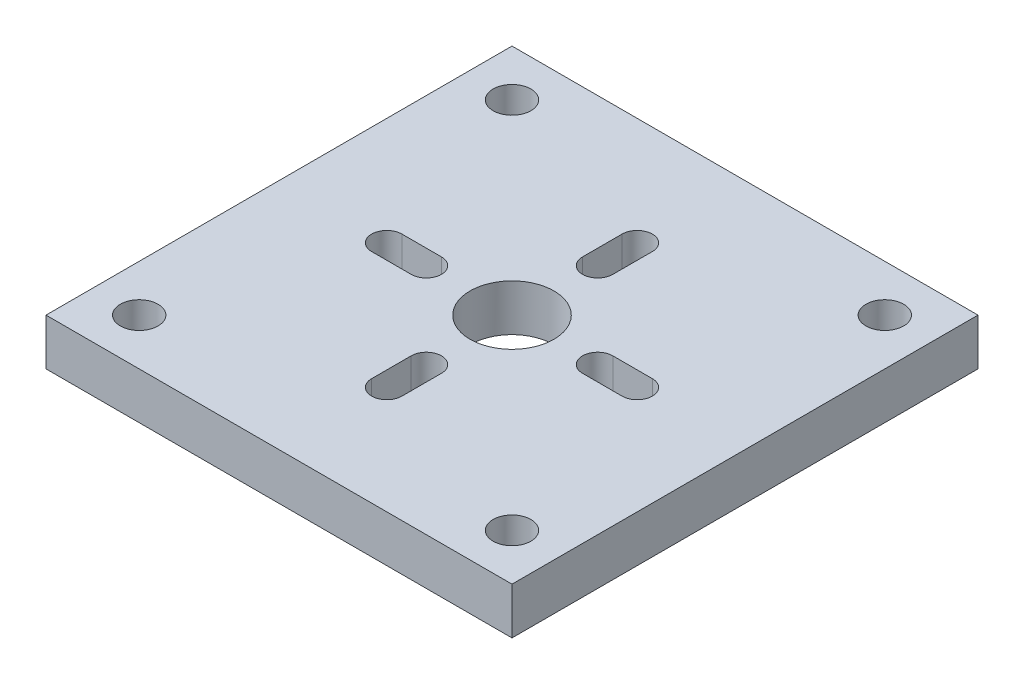
SolidWorks part; units mm, degrees
ref_plane "Front Plane" through (0, 0, 0) normal (0, 0, 1) x (1, 0, 0)
ref_plane "Top Plane" through (0, 0, 0) normal (0, 1, 0) x (1, 0, 0)
ref_plane "Right Plane" through (0, 0, 0) normal (1, 0, 0) x (0, 0, -1)
sketch "Sketch1" plane through (0, 0, 0) normal (0, 1, 0) x (1, 0, 0)
  line L1 (50, 50) -> (-50, 50)
  line L2 (50, 50) -> (50, -50)
  line L3 (50, -50) -> (-50, -50)
  line L4 (-50, 50) -> (-50, -50)
  line L5 (50, 50) -> (-50, -50) construction
  line L6 (50, -50) -> (-50, 50) construction
  point P0 (0, 0)
  dimension "D1" = 100
  dimension "D2" = 100
extrude "base" add sketch "Sketch1" along normal blind 10 contours L1 L4 L3 L2
sketch "Sketch2" plane through (0, 10, 0) normal (0, 1, 0) x (1, 0, 0)
  circle A0 centre (0, 0) radius 9
  dimension "D1" = 18
extrude "actuator cut" cut sketch "Sketch2" against normal blind 40
sketch "Sketch3" plane through (0, 10, 0) normal (0, 1, 0) x (1, 0, 0)
  line L0 (0, -26.8701) -> (0, -18.3848) construction
  line L1 (0, 0) -> (0, 19) construction
  line L2 (3.25, -26.8701) -> (3.25, -18.3848)
  line L8 (0, 0) -> (19, 0) construction
  line L12 (-3.25, -26.8701) -> (-3.25, -18.3848)
  line L17 (26.8701, 0) -> (18.3848, 0) construction
  line L18 (26.8701, 3.25) -> (18.3848, 3.25)
  line L19 (26.8701, -3.25) -> (18.3848, -3.25)
  line L20 (-26.8701, 0) -> (-18.3848, 0) construction
  line L21 (-26.8701, -3.25) -> (-18.3848, -3.25)
  line L22 (-26.8701, 3.25) -> (-18.3848, 3.25)
  line L23 (0, 26.8701) -> (0, 18.3848) construction
  line L24 (-3.25, 26.8701) -> (-3.25, 18.3848)
  line L25 (3.25, 26.8701) -> (3.25, 18.3848)
  arc A16 (26.8701, 3.25) -> (26.8701, -3.25) centre (26.8701, 0) cw
  arc A17 (18.3848, -3.25) -> (18.3848, 3.25) centre (18.3848, 0) cw
  arc A18 (3.25, -26.8701) -> (-3.25, -26.8701) centre (0, -26.8701) cw
  arc A19 (-3.25, -18.3848) -> (3.25, -18.3848) centre (0, -18.3848) cw
  arc A20 (-26.8701, -3.25) -> (-26.8701, 3.25) centre (-26.8701, 0) cw
  arc A21 (-18.3848, 3.25) -> (-18.3848, -3.25) centre (-18.3848, 0) cw
  arc A22 (-3.25, 26.8701) -> (3.25, 26.8701) centre (0, 26.8701) cw
  arc A23 (3.25, 18.3848) -> (-3.25, 18.3848) centre (0, 18.3848) cw
  point P5 (0, -22.6274)
  point P15 (-22.6274, 0)
  point P23 (0, 22.6274)
  point P30 (22.6274, 0)
  point P35 (0, 0)
  dimension "D1" = 26.8701
  dimension "D3" = 3.25
  dimension "D2" = 18.3848
  dimension "D4" = 4
  dimension "D7" = 0
extrude "Cut-Extrude1" cut sketch "Sketch3" against normal up to next
sketch "Sketch4" [suppressed] plane through (0, 0, 0) normal (0, -1, 0) x (1, 0, 0)
  line L0 (2.373, 19) -> (2.373, 13) construction
  line L1 (-4.127, 13) -> (-4.127, 19) construction
  line L2 (13, 6.377) -> (19, 6.377)
  line L3 (19, -5.123) -> (13, -5.123)
  line L4 (6.377, -13.25) -> (6.377, -19.25)
  line L5 (-5.123, -19.25) -> (-5.123, -13.25)
  line L6 (-13.25, -6.627) -> (-19.25, -6.627)
  line L7 (-19.25, 4.873) -> (-13.25, 4.873)
  line L8 (2.373, 19) -> (2.373, 13) construction
  line L9 (-4.127, 13) -> (-4.127, 19) construction
  line L16 (4.873, 19) -> (4.873, 13)
  line L17 (-6.627, 13) -> (-6.627, 19)
  arc A0 (-4.127, 13) -> (2.373, 13) centre (-0.877, 13) ccw construction
  arc A1 (2.373, 19) -> (-4.127, 19) centre (-0.877, 19) ccw construction
  arc A2 (13, 6.377) -> (13, -5.123) centre (13, 0.627) ccw
  arc A3 (19, -5.123) -> (19, 6.377) centre (19, 0.627) ccw
  arc A4 (6.377, -13.25) -> (-5.123, -13.25) centre (0.627, -13.25) ccw
  arc A5 (-5.123, -19.25) -> (6.377, -19.25) centre (0.627, -19.25) ccw
  arc A6 (-13.25, -6.627) -> (-13.25, 4.873) centre (-13.25, -0.877) ccw
  arc A7 (-19.25, 4.873) -> (-19.25, -6.627) centre (-19.25, -0.877) ccw
  arc A8 (-4.127, 13) -> (2.373, 13) centre (-0.877, 13) ccw construction
  arc A9 (2.373, 19) -> (-4.127, 19) centre (-0.877, 19) ccw construction
  arc A16 (-6.627, 13) -> (4.873, 13) centre (-0.877, 13) ccw
  arc A17 (4.873, 19) -> (-6.627, 19) centre (-0.877, 19) ccw
  point P33 (-0.125, -0.125)
  dimension "D1" = 2.5
  dimension "D2" = 4
split line "Split Line1" [suppressed]
sketch "Sketch5" plane through (0, 10, 0) normal (0, 1, 0) x (1, 0, 0)
  line L0 (-40, 40) -> (-40, -40) construction
  line L1 (-40, -40) -> (40, -40) construction
  circle A0 centre (-40, -40) radius 4.05
  circle A1 centre (-40, 40) radius 4.05
  circle A2 centre (40, -40) radius 4.05
  circle A3 centre (40, 40) radius 4.05
  point P8 (-40, 0)
  point P9 (0, -40)
  dimension "D3" = 8.1
  dimension "D1" = 80
  dimension "D2" = 80
extrude "Cut-Extrude2" cut sketch "Sketch5" against normal up to next
sketch "Sketch6" [suppressed] plane through (0, 0, 0) normal (0, -1, 0) x (1, 0, 0)
  circle A0 centre (-40, 40) radius 4
  circle A1 centre (40, 40) radius 4
  circle A2 centre (40, -40) radius 4
  circle A3 centre (-40, -40) radius 4
  dimension "D1" = 8
extrude "Cut-Extrude3" [suppressed] cut sketch "Sketch6" against normal through all
sketch "Sketch7" [suppressed] plane through (0, 0, 0) normal (0, -1, 0) x (1, 0, 0)
  line L175 (6.25, -26.8701) -> (6.25, -18.3848)
  line L176 (-6.25, -18.3848) -> (-6.25, -26.8701)
  line L177 (18.3848, -6.25) -> (26.8701, -6.25)
  line L178 (26.8701, 6.25) -> (18.3848, 6.25)
  line L179 (18.3848, -6.25) -> (26.8701, -6.25)
  line L180 (26.8701, 6.25) -> (18.3848, 6.25)
  line L181 (-26.8701, -6.25) -> (-18.3848, -6.25)
  line L182 (-18.3848, 6.25) -> (-26.8701, 6.25)
  line L183 (-6.25, 26.8701) -> (-6.25, 18.3848)
  line L184 (6.25, 18.3848) -> (6.25, 26.8701)
  arc A173 (-6.25, -26.8701) -> (6.25, -26.8701) centre (0, -26.8701) ccw
  arc A174 (6.25, -18.3848) -> (-6.25, -18.3848) centre (0, -18.3848) ccw
  arc A175 (26.8701, -6.25) -> (26.8701, 6.25) centre (26.8701, 0) ccw
  arc A176 (18.3848, 6.25) -> (18.3848, -6.25) centre (18.3848, 0) ccw
  arc A177 (26.8701, -6.25) -> (26.8701, 6.25) centre (26.8701, 0) ccw
  arc A178 (18.3848, 6.25) -> (18.3848, -6.25) centre (18.3848, 0) ccw
  arc A179 (-26.8701, 6.25) -> (-26.8701, -6.25) centre (-26.8701, 0) ccw
  arc A180 (-18.3848, -6.25) -> (-18.3848, 6.25) centre (-18.3848, 0) ccw
  arc A181 (6.25, 26.8701) -> (-6.25, 26.8701) centre (0, 26.8701) ccw
  arc A182 (-6.25, 18.3848) -> (6.25, 18.3848) centre (0, 18.3848) ccw
  point P21 (0, 0)
  dimension "D1" = 3
  dimension "D2" = 4
split line "Split Line2" [suppressed]
